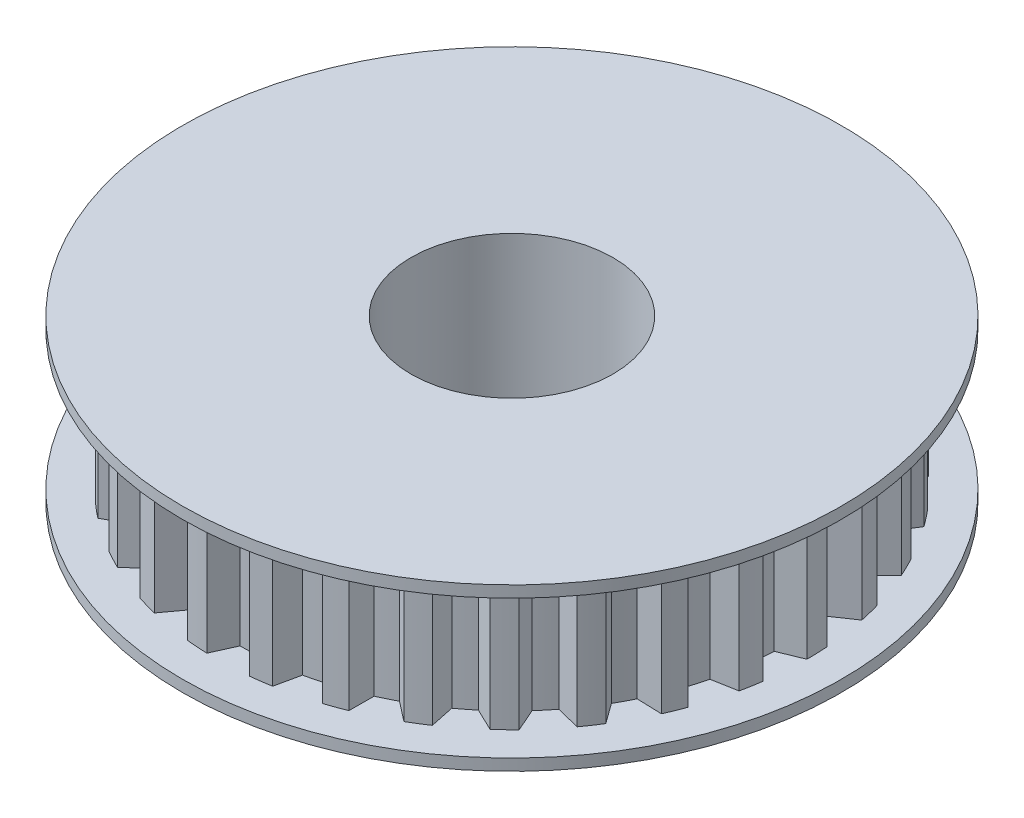
SolidWorks part; units mm, degrees
ref_plane "Front Plane" through (0, 0, 0) normal (0, 0, 1) x (1, 0, 0)
ref_plane "Top Plane" through (0, 0, 0) normal (0, 1, 0) x (1, 0, 0)
ref_plane "Right Plane" through (0, 0, 0) normal (1, 0, 0) x (0, 0, -1)
sketch "Sketch1" plane through (0, 0, 0) normal (0, 1, 0) x (1, 0, 0)
  circle A0 centre (0, 0) radius 28.575
  dimension "D1" = 57.15
extrude "Boss-Extrude1" add sketch "Sketch1" along normal blind 1
sketch "Sketch2" plane through (0, 1, 0) normal (0, 1, 0) x (1, 0, 0)
  line L0 (0, 0) -> (25.575, 0)
  line L4 (0, 0) -> (25.0161, 5.3173)
  line L5 (25.5127, 1.784) -> (23.4459, 2.4643)
  line L6 (25.0161, 5.3173) -> (23.2168, 4.0938)
  arc A0 (25.575, 0) -> (25.5127, 1.784) centre (0, 0) ccw
  circle A3 centre (0, 0) radius 28.575 construction
  arc A4 (23.4459, 2.4643) -> (23.2168, 4.0938) centre (0, 0) ccw
  dimension "D1" = 3
  dimension "D2" = 12
extrude "Boss-Extrude3" add sketch "Sketch2" along normal blind 12
pattern_circular "CirPattern2" count 30 over 360 about axis through (0, 1, 0) along (0, -1, 0) of "Boss-Extrude3"
sketch "Sketch3" plane through (0, 13, 0) normal (0, 1, 0) x (1, 0, 0)
  circle A0 centre (0, 0) radius 28.575
  circle A1 centre (0, 0) radius 28.575 construction
  dimension "D1" = 0
extrude "Boss-Extrude4" add sketch "Sketch3" along normal blind 1
sketch "Sketch4" plane through (0, 14, 0) normal (0, 1, 0) x (1, 0, 0)
  circle A0 centre (0, 0) radius 8.7586
extrude "Cut-Extrude1" cut sketch "Sketch4" against normal up to next
